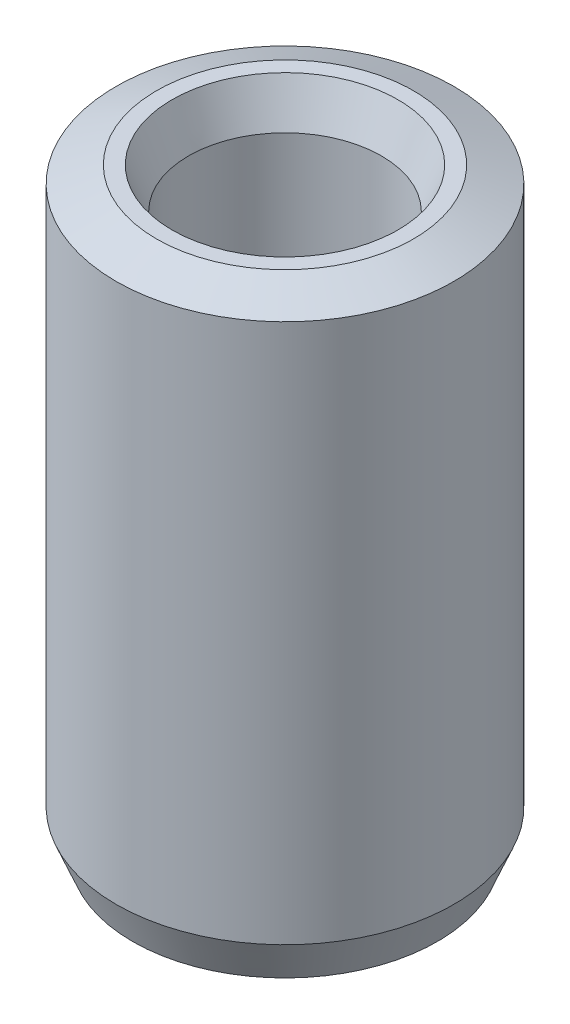
SolidWorks part; units mm, degrees
ref_plane "Front Plane" through (0, 0, 0) normal (0, 0, 1) x (1, 0, 0)
ref_plane "Top Plane" through (0, 0, 0) normal (0, 1, 0) x (1, 0, 0)
ref_plane "Right Plane" through (0, 0, 0) normal (1, 0, 0) x (0, 0, -1)
sketch "Sketch1" plane through (0, 0, 0) normal (0, 1, 0) x (1, 0, 0)
  circle A0 centre (0, 0) radius 15
  dimension "SLEEVE_OD" = 30
extrude "Boss-Extrude1" add sketch "Sketch1" along normal blind 52.9691
sketch "Sketch2" plane through (0, 0, 0) normal (0, 1, 0) x (1, 0, 0)
  circle A0 centre (0, 0) radius 8.5622
  dimension "BORE_D" = 17.1243
extrude "Cut-Extrude1" cut sketch "Sketch2" along normal through all
chamfer "Chamfer1" distance 1.4665 angle 67.787 4 edges at (0, 52.9691, 8.5622) (0, 0, 8.5622) (0, 0, 15) (0, 52.9691, 15) first distance on face at (0, 52.9691, 8.5622) first distance on face at (0, 0, 8.5622) first distance on face at (0, 52.9691, 15)
